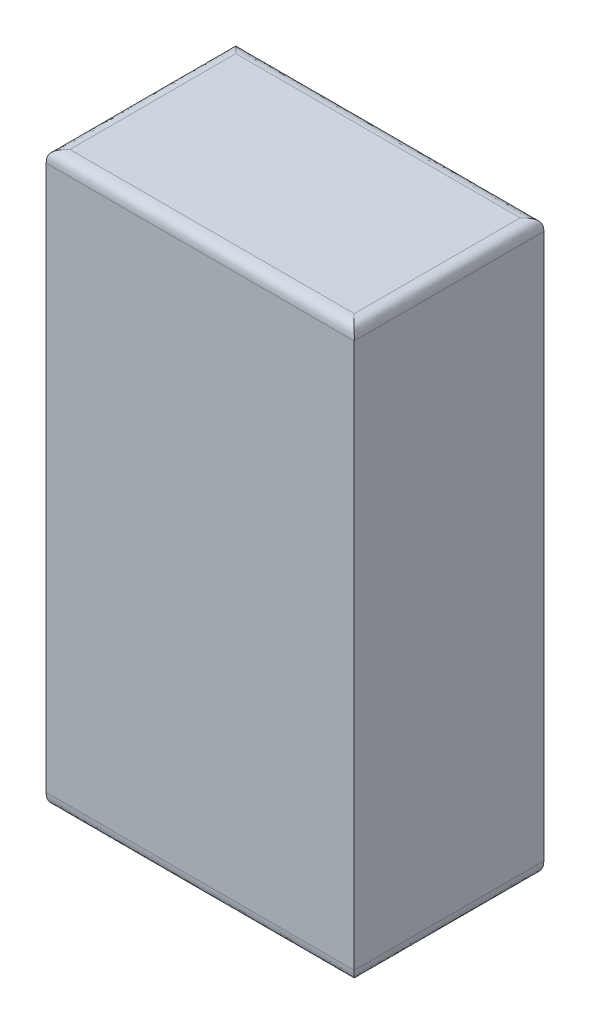
SolidWorks part; units mm, degrees
ref_plane "Front Plane" through (0, 0, 0) normal (0, 0, 1) x (1, 0, 0)
ref_plane "Top Plane" through (0, 0, 0) normal (0, 1, 0) x (1, 0, 0)
ref_plane "Right Plane" through (0, 0, 0) normal (1, 0, 0) x (0, 0, -1)
sketch "Sketch1" plane through (0, 0, 0) normal (0, 0, 1) x (1, 0, 0)
  line L1 (-24.5324, 17.8118) -> (1.4676, 17.8118)
  line L2 (-24.5324, 17.8118) -> (-24.5324, -30.1882)
  line L3 (-24.5324, -30.1882) -> (1.4676, -30.1882)
  line L4 (1.4676, 17.8118) -> (1.4676, -30.1882)
  dimension "D1" = 48
  dimension "D2" = 26
extrude "Boss-Extrude1" add sketch "Sketch1" along normal blind 16
fillet "Fillet1" radius 1 8 edges at (-24.5324, -30.1882, 8) (-11.5324, -30.1882, 0) (-11.5324, -30.1882, 16) (1.4676, -30.1882, 8) (-11.5324, 17.8118, 0) (1.4676, 17.8118, 8) (-11.5324, 17.8118, 16) (-24.5324, 17.8118, 8) curvature continuous yes
